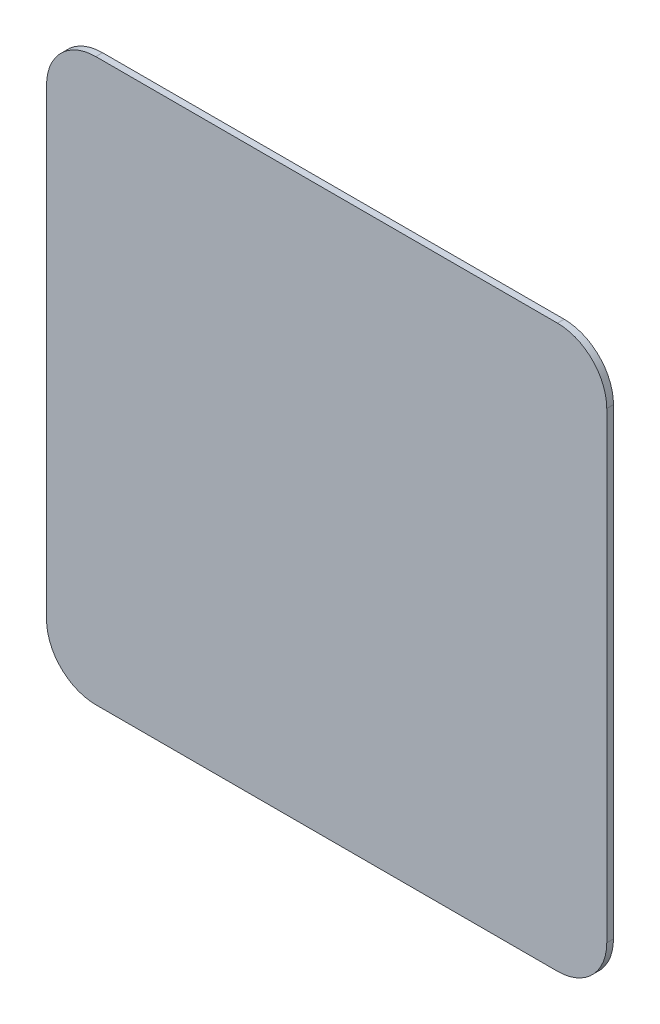
SolidWorks part; units mm, degrees
material "Pine"
ref_plane "Front Plane" through (0, 0, 0) normal (0, 0, 1) x (1, 0, 0)
ref_plane "Top Plane" through (0, 0, 0) normal (0, 1, 0) x (1, 0, 0)
ref_plane "Right Plane" through (0, 0, 0) normal (1, 0, 0) x (0, 0, -1)
sketch "Sketch1" plane through (0, 0, 0) normal (0, 0, 1) x (1, 0, 0)
  line L1 (0, 0) -> (500, 0)
  line L2 (0, 0) -> (0, 501)
  line L3 (0, 501) -> (500, 501)
  line L4 (500, 0) -> (500, 501)
  dimension "D1" = 500
  dimension "D2" = 501
extrude "Boss-Extrude1" add sketch "Sketch1" along normal blind 6
fillet "Fillet1" radius 44 4 edges at (0, 0, 3) (0, 501, 3) (500, 0, 3) (500, 501, 3)
